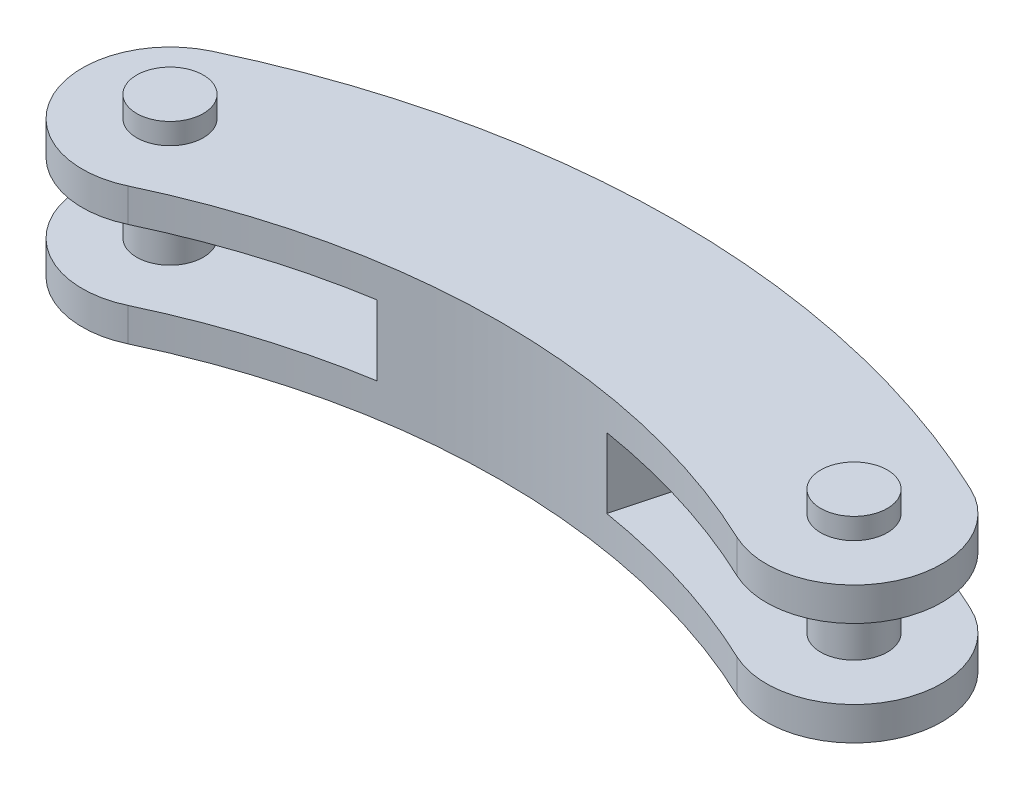
SolidWorks part; units mm, degrees
ref_plane "Front Plane" through (0, 0, 0) normal (0, 0, 1) x (1, 0, 0)
ref_plane "Top Plane" through (0, 0, 0) normal (0, 1, 0) x (1, 0, 0)
ref_plane "Right Plane" through (0, 0, 0) normal (1, 0, 0) x (0, 0, -1)
sketch "Sketch1" plane through (0, 0, 0) normal (0, 1, 0) x (1, 0, 0)
  line L0 (-97.5, -21.8987) -> (97.5, -21.8987) construction
  arc A0 (-97.5, -21.8987) -> (97.5, -21.8987) centre (0, -228) cw construction
  arc A1 (108.1908, 0.7001) -> (-108.1908, 0.7001) centre (0, -228) ccw
  arc A2 (86.8092, -44.4975) -> (-86.8092, -44.4975) centre (0, -228) ccw
  arc A3 (86.8092, -44.4975) -> (108.1908, 0.7001) centre (97.5, -21.8987) ccw
  arc A4 (-108.1908, 0.7001) -> (-86.8092, -44.4975) centre (-97.5, -21.8987) ccw
  point P3 (0, 0)
  dimension "D2" = 195
  dimension "D1" = 203
  dimension "D3" = 25
extrude "Boss-Extrude1" add sketch "Sketch1" along normal blind 9.5 contours A1 A4 A2 A3
sketch "Sketch2" plane through (0, 9.5, 0) normal (0, 1, 0) x (1, 0, 0)
  line L0 (0, 78.4783) -> (0, -150) construction
  line L1 (0, -150) -> (-45.7724, 20.825)
  line L2 (0, -150) -> (45.7724, 20.825)
  arc A0 (86.8092, -44.4975) -> (-86.8092, -44.4975) centre (0, -228) ccw construction
  arc A1 (108.1908, 0.7001) -> (-108.1908, 0.7001) centre (0, -228) ccw construction
  arc A2 (86.8092, -44.4975) -> (-86.8092, -44.4975) centre (0, -228) ccw
  arc A3 (108.1908, 0.7001) -> (-108.1908, 0.7001) centre (0, -228) ccw
  arc M4 (108.1908, 0.7001) -> (-108.1908, 0.7001) centre (0, -228) ccw
  arc M6 (-86.8092, -44.4975) -> (86.8092, -44.4975) centre (0, -228) cw
  dimension "D1" = 15
  dimension "D2" = 150
extrude "Boss-Extrude2" add sketch "Sketch2" along normal blind 20 contours L0 A2 L2 M4 | L0 A3 L1 M6 region at (19.8688, 9.5, -0.2303) region at (-19.8688, 9.5, -0.2303)
sketch "Sketch3" plane through (0, 29.5, 0) normal (0, 1, 0) x (1, 0, 0)
  arc A4 (108.1908, 0.7001) -> (-108.1908, 0.7001) centre (0, -228) ccw
  arc A5 (-108.1908, 0.7001) -> (-86.8092, -44.4975) centre (-97.5, -21.8987) ccw
  arc A6 (86.8092, -44.4975) -> (-86.8092, -44.4975) centre (0, -228) ccw
  arc A7 (86.8092, -44.4975) -> (108.1908, 0.7001) centre (97.5, -21.8987) ccw
  arc A8 (108.1908, 0.7001) -> (-108.1908, 0.7001) centre (0, -228) ccw
  arc A9 (-108.1908, 0.7001) -> (-86.8092, -44.4975) centre (-97.5, -21.8987) ccw
  arc A10 (86.8092, -44.4975) -> (-86.8092, -44.4975) centre (0, -228) ccw
  arc A11 (86.8092, -44.4975) -> (108.1908, 0.7001) centre (97.5, -21.8987) ccw
  dimension "D1" = 0
extrude "Boss-Extrude3" add sketch "Sketch3" along normal blind 9.5
sketch "Sketch4" plane through (0, 39, 0) normal (0, 1, 0) x (1, 0, 0)
  circle A0 centre (-97.5, -21.8987) radius 9.5
  circle A1 centre (97.5, -21.8987) radius 9.5
  dimension "D1" = 19
extrude "Cut-Extrude1" cut sketch "Sketch4" against normal through all
extrude "Boss-Extrude4" add sketch "Sketch4<2>" against normal blind 50 from offset 6 separate body
sketch "Sketch4<2>" plane through (0, 39, 0) normal (0, 1, 0) x (1, 0, 0) same geometry as "Sketch4"
